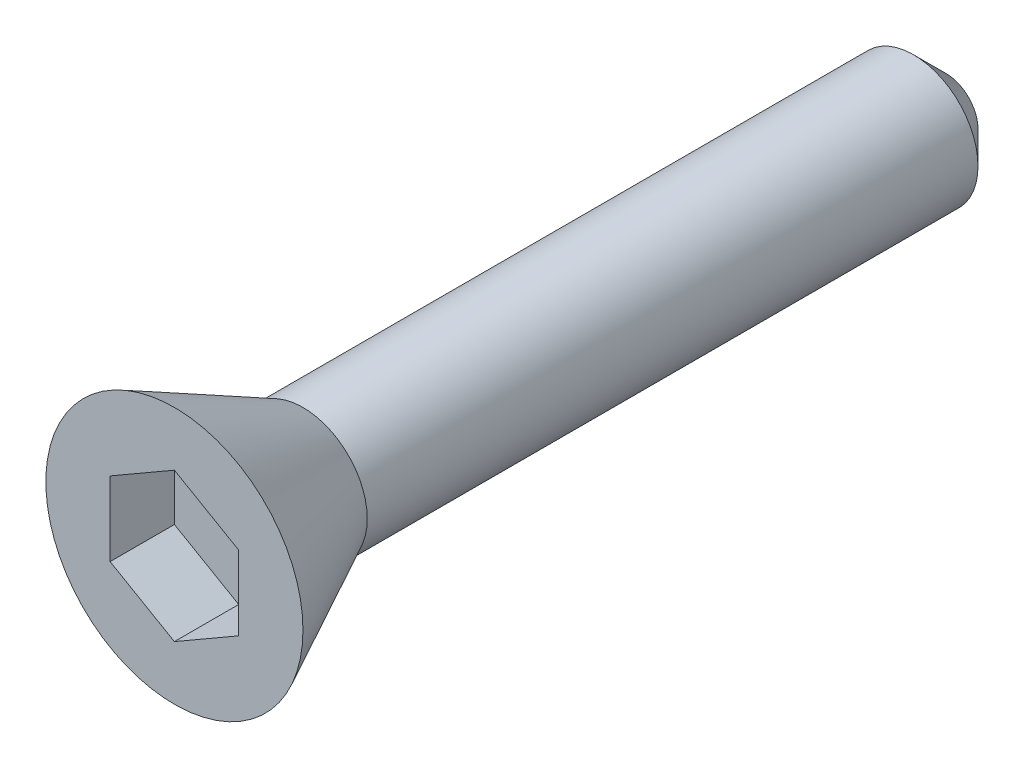
SolidWorks part; units mm, degrees
ref_plane "Front Plane" through (0, 0, 0) normal (0, 0, 1) x (1, 0, 0)
ref_plane "Top Plane" through (0, 0, 0) normal (0, 1, 0) x (1, 0, 0)
ref_plane "Right Plane" through (0, 0, 0) normal (1, 0, 0) x (0, 0, -1)
sketch "Sketch1" plane through (0, 0, 0) normal (1, 0, 0) x (0, 0, -1)
  line L0 (-58.5147, 0) -> (2867.2225, 0) construction
  line L1 (0, 0) -> (0, 2)
  line L2 (0, 2) -> (2, 1)
  line L3 (2, 1) -> (12, 1)
  line L4 (12, 1) -> (12, 0)
  line L5 (12, 0) -> (0, 0)
  point P5 (1.3286, 1)
  dimension "D1" = 2
  dimension "D2" = 4
  dimension "D3" = 10
  dimension "D4" = 2
revolve "Body" add sketch "Sketch1" angle 360 about L0
sketch "Sketch2" plane through (0, 0, 0) normal (0, 0, 1) x (1, 0, 0)
  line L1 (0, 1.1547) -> (-1, 0.5774)
  line L2 (-1, 0.5774) -> (-1, -0.5774)
  line L3 (-1, -0.5774) -> (0, -1.1547)
  line L4 (0, -1.1547) -> (1, -0.5774)
  line L5 (1, -0.5774) -> (1, 0.5774)
  line L6 (1, 0.5774) -> (0, 1.1547)
  circle A0 centre (0, 0) radius 1 construction
  point P1 (0, 0)
  dimension "D1" = 2
extrude "Footprint" cut sketch "Sketch2" against normal blind 1
chamfer "Chamfer1" distance 0.5 angle 45 1 edges at (1, 0, -12)
